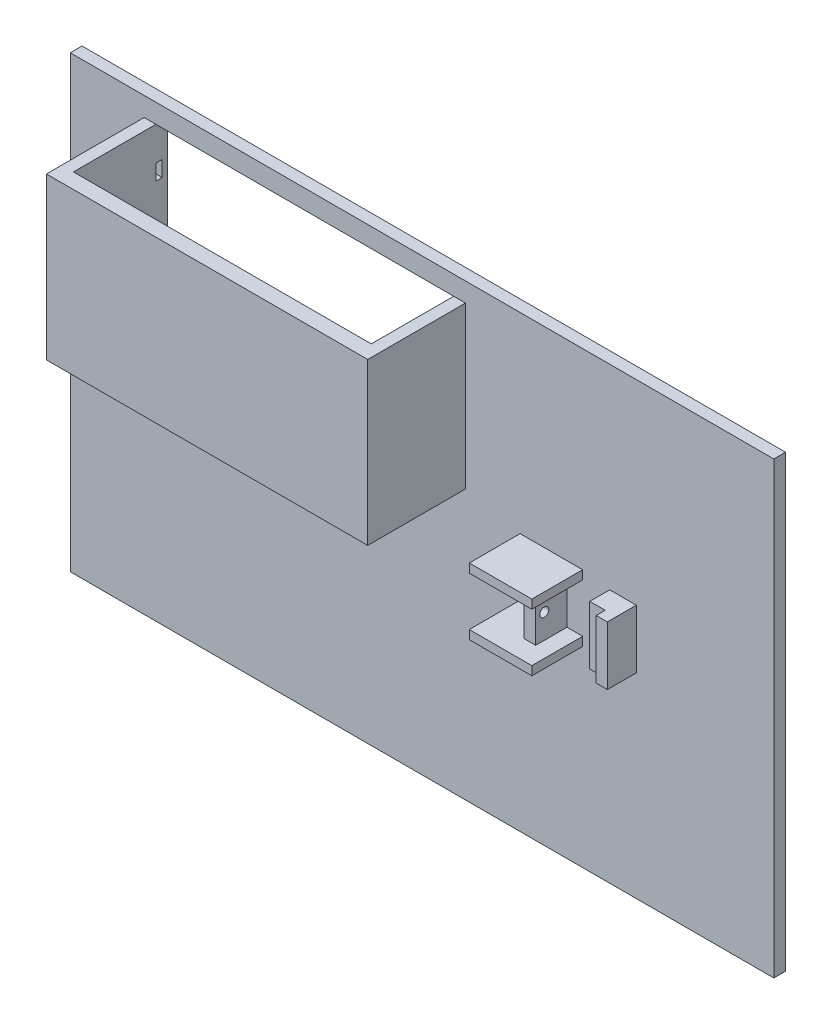
SolidWorks part; units mm, degrees
ref_plane "前视基准面" through (0, 0, 0) normal (0, 0, 1) x (1, 0, 0)
ref_plane "上视基准面" through (0, 0, 0) normal (0, 1, 0) x (1, 0, 0)
ref_plane "右视基准面" through (0, 0, 0) normal (1, 0, 0) x (0, 0, -1)
sketch "草图1" plane through (0, 0, 0) normal (0, 0, 1) x (1, 0, 0)
  line L1 (-90, 57.5) -> (90, 57.5)
  line L2 (-90, 57.5) -> (-90, -57.5)
  line L3 (-90, -57.5) -> (90, -57.5)
  line L4 (90, 57.5) -> (90, -57.5)
  line L5 (-90, 57.5) -> (90, -57.5) construction
  line L6 (-90, -57.5) -> (90, 57.5) construction
  point P0 (0, 0)
  dimension "D1" = 115
  dimension "D2" = 180
extrude "凸台-拉伸1" add sketch "草图1" along normal blind 3
sketch "草图7" plane through (0, 0, 0) normal (0, 0, -1) x (-1, 0, 0)
  line L0 (-90, 57.5) -> (90, 57.5) construction
  line L1 (-8.1, 52.6) -> (68.1, 52.6)
  line L2 (-8.1, 52.6) -> (-8.1, 11.4)
  line L3 (-8.1, 11.4) -> (68.1, 11.4)
  line L4 (68.1, 52.6) -> (68.1, 11.4)
  line L5 (90, 57.5) -> (90, -57.5) construction
  dimension "D1" = 41.2
  dimension "D2" = 76.2
  dimension "D3" = 4.9
  dimension "D4" = 21.9
extrude "电池位切除-拉伸3" cut sketch "草图7" against normal up to next
sketch "草图4" plane through (0, 0, 0) normal (0, 0, -1) x (-1, 0, 0)
  line L0 (68.1, 11.4) -> (68.1, 52.6) construction
  line L5 (68.1, 32) -> (94.8483, 32) construction
  line L10 (83.2374, -53.4277) -> (79.3374, -53.4277) construction
  line L11 (83.2374, -49.6277) -> (83.2374, -53.4277) construction
  line L12 (79.3374, -49.6277) -> (83.2374, -49.6277) construction
  line L13 (68.1, 20) -> (68.1, 24)
  line L20 (72.1, 20) -> (68.1, 20)
  line L21 (72.1, 24) -> (72.1, 20)
  line L22 (68.1, 24) -> (72.1, 24)
  line L29 (68.1, 40) -> (72.1, 40)
  line L30 (72.1, 40) -> (72.1, 44)
  line L31 (72.1, 44) -> (68.1, 44)
  line L32 (68.1, 44) -> (68.1, 40)
  point P6 (70.1, 40)
  dimension "D1" = 4
  dimension "D2" = 4
  dimension "D3" = 8
extrude "切除-拉伸2" cut sketch "草图4" along normal blind 1.6 from surface starting at face at (-30, 32, 3)
sketch "草图8" plane through (0, 0, 3) normal (0, 0, 1) x (1, 0, 0)
  line L0 (-68.1, 11.4) -> (-68.1, 20) construction
  line L1 (11.1, 11.4) -> (8.1, 11.4)
  line L2 (11.1, 11.4) -> (11.1, 52.6)
  line L3 (11.1, 52.6) -> (8.1, 52.6)
  line L4 (8.1, 11.4) -> (8.1, 52.6)
  line L5 (-68.1, 11.4) -> (-71.1, 11.4)
  line L6 (-68.1, 11.4) -> (-68.1, 52.6)
  line L7 (-68.1, 52.6) -> (-71.1, 52.6)
  line L8 (-71.1, 11.4) -> (-71.1, 52.6)
  line L9 (-68.1, 52.6) -> (8.1, 52.6) construction
  line L10 (8.1, 11.4) -> (-68.1, 11.4) construction
  line L11 (8.1, 52.6) -> (8.1, 11.4) construction
  dimension "D1" = 3
extrude "凸台-拉伸2" add sketch "草图8" along normal blind 25
sketch "草图9" plane through (0, 0, 28) normal (0, 0, 1) x (1, 0, 0)
  line L1 (11.1, 11.4) -> (-71.1, 11.4)
  line L2 (11.1, 11.4) -> (11.1, 52.6)
  line L3 (11.1, 52.6) -> (-71.1, 52.6)
  line L4 (-71.1, 11.4) -> (-71.1, 52.6)
extrude "凸台-拉伸3" add sketch "草图9" against normal blind 3.9
sketch "草图10" plane through (0, 0, 3) normal (0, 0, 1) x (1, 0, 0)
  line L0 (48, 5.975) -> (48, 68.325) construction
  line L1 (54.8, -7.5) -> (48, -7.5)
  line L2 (54.8, -7.5) -> (54.8, 7.5)
  line L3 (54.8, 7.5) -> (48, 7.5)
  line L4 (48, -7.5) -> (48, 7.5)
  line L7 (15, 9.5) -> (71.1, 9.5) construction
  dimension "D1" = 15
  dimension "D2" = 6.8
  dimension "D3" = 2
extrude "变速杆凸台-拉伸4" add sketch "草图10" along normal offset from surface (5.1 mm away) 0.1
sketch "草图11" plane through (0, 0, 8.1) normal (0, 0, 1) x (1, 0, 0)
  line L0 (54.8, -7.5) -> (48, -7.5) construction
  line L1 (54.8, -7.5) -> (51.95, -7.5)
  line L2 (54.8, -7.5) -> (54.8, 7.5)
  line L3 (54.8, 7.5) -> (51.95, 7.5)
  line L4 (51.95, -7.5) -> (51.95, 7.5)
  line L5 (54.8, 7.5) -> (54.8, -7.5) construction
  line L6 (48, 7.5) -> (54.8, 7.5) construction
  line L7 (51.8, 68.325) -> (51.8, 5.975) construction
  dimension "D1" = 0.15
extrude "变速杆前档凸台-拉伸5" add sketch "草图11" along normal blind 2.3
sketch "草图12" plane through (0, 0, 3) normal (0, 0, 1) x (1, 0, 0)
  line L0 (39.5974, -6.096) -> (37.2352, -6.096) construction
  line L1 (37.0852, -8.5) -> (25.0852, -8.5)
  line L3 (34.0852, -6.246) -> (25.0852, -6.246)
  line L4 (25.0852, -8.5) -> (25.0852, -6.246)
  line L5 (34.0852, 6.246) -> (25.0852, 6.246)
  line L7 (37.0852, 8.5) -> (25.0852, 8.5)
  line L8 (25.0852, 6.246) -> (25.0852, 8.5)
  line L9 (37.2352, 6.096) -> (39.5974, 6.096) construction
  line L10 (15, 9.5) -> (71.1, 9.5) construction
  line L13 (37.2352, -0.635) -> (37.2352, -5.461) construction
  line L15 (37.0852, -6.246) -> (37.0852, 6.246)
  line L17 (34.0852, -6.246) -> (34.0852, 6.246)
  line L19 (37.0852, 8.5) -> (41.0852, 8.5)
  line L21 (37.0852, 6.246) -> (41.0852, 6.246)
  line L22 (41.0852, 8.5) -> (41.0852, 6.246)
  line L23 (37.0852, -6.246) -> (41.0852, -6.246)
  line L25 (37.0852, -8.5) -> (41.0852, -8.5)
  line L26 (41.0852, -6.246) -> (41.0852, -8.5)
  point P12 (38.4163, 6.096)
  dimension "D1" = 0.15
  dimension "D2" = 0.15
  dimension "D3" = 1
  dimension "D4" = 2.254
  dimension "D5" = 4
  dimension "D7" = 0.15
  dimension "D8" = 3
  dimension "D9" = 9
extrude "变速舵机底座凸台-拉伸6" add sketch "草图12" along normal offset from surface (8.004 mm away) 0.1
sketch "草图13" plane through (0, 0, 11.004) normal (0, 0, 1) x (1, 0, 0)
  line L0 (25.0852, -8.5) -> (41.0852, -8.5) construction
  line L1 (25.0852, -8.5) -> (41.0852, -8.5)
  line L2 (34.0852, -6.246) -> (25.0852, -6.246) construction
  line L3 (34.0852, -6.246) -> (25.0852, -6.246)
  line L4 (41.0852, -8.5) -> (41.0852, -6.246) construction
  line L5 (41.0852, -8.5) -> (41.0852, -6.246)
  line L6 (25.0852, -6.246) -> (25.0852, -8.5) construction
  line L7 (25.0852, -6.246) -> (25.0852, -8.5)
  line L8 (41.0852, 8.5) -> (25.0852, 8.5) construction
  line L9 (41.0852, 8.5) -> (25.0852, 8.5)
  line L10 (25.0852, 8.5) -> (25.0852, 6.246) construction
  line L11 (25.0852, 8.5) -> (25.0852, 6.246)
  line L12 (25.0852, 6.246) -> (34.0852, 6.246) construction
  line L13 (25.0852, 6.246) -> (34.0852, 6.246)
  line L14 (41.0852, 6.246) -> (41.0852, 8.5) construction
  line L15 (41.0852, 6.246) -> (41.0852, 8.5)
  line L16 (34.0852, -6.246) -> (41.0852, -6.246)
  line L17 (34.0852, 6.246) -> (41.0852, 6.246)
extrude "变速舵机卡位凸台-拉伸7" add sketch "草图13" along normal blind 5
sketch "草图15" plane through (34.0852, 0, 0) normal (-1, 0, 0) x (0, 0, 1)
  circle A0 centre (8.818, 0) radius 1.15
  dimension "D1" = 2.3
extrude "变速舵机螺丝孔切除-拉伸7" cut sketch "草图15" against normal up to next
